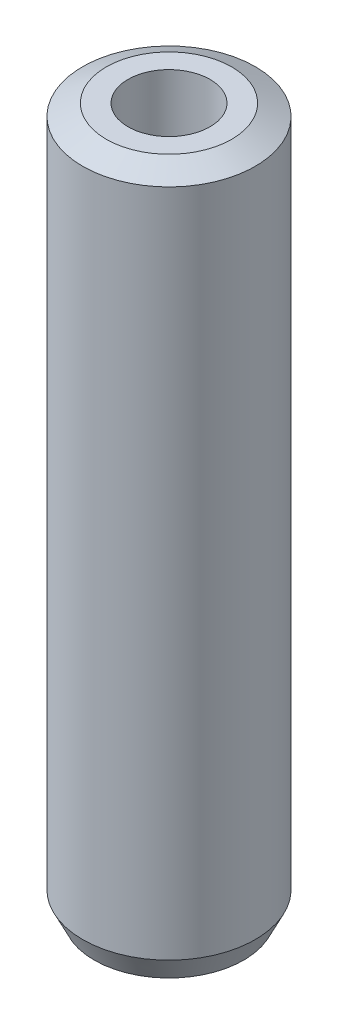
SolidWorks part; units mm, degrees
ref_plane "Front Plane" through (0, 0, 0) normal (0, 0, 1) x (1, 0, 0)
ref_plane "Top Plane" through (0, 0, 0) normal (0, 1, 0) x (1, 0, 0)
ref_plane "Right Plane" through (0, 0, 0) normal (1, 0, 0) x (0, 0, -1)
sketch "Sketch1" plane through (0, 0, 0) normal (0, 1, 0) x (1, 0, 0)
  circle A0 centre (0, 0) radius 7.5
  dimension "SHAFT_OD" = 15
extrude "Boss-Extrude1" add sketch "Sketch1" along normal blind 61.235
sketch "Sketch2" plane through (0, 0, 0) normal (0, 1, 0) x (1, 0, 0)
  circle A0 centre (0, 0) radius 3.5656
  dimension "BORE_D" = 7.1312
extrude "Cut-Extrude1" cut sketch "Sketch2" along normal through all
chamfer "Chamfer1" distance 1.006 angle 63.895 2 edges at (0, 61.235, 7.5) (0, 0, 7.5) first distance on face at (0, 61.235, 7.5) first distance on face at (0, 0, 3.5656)
